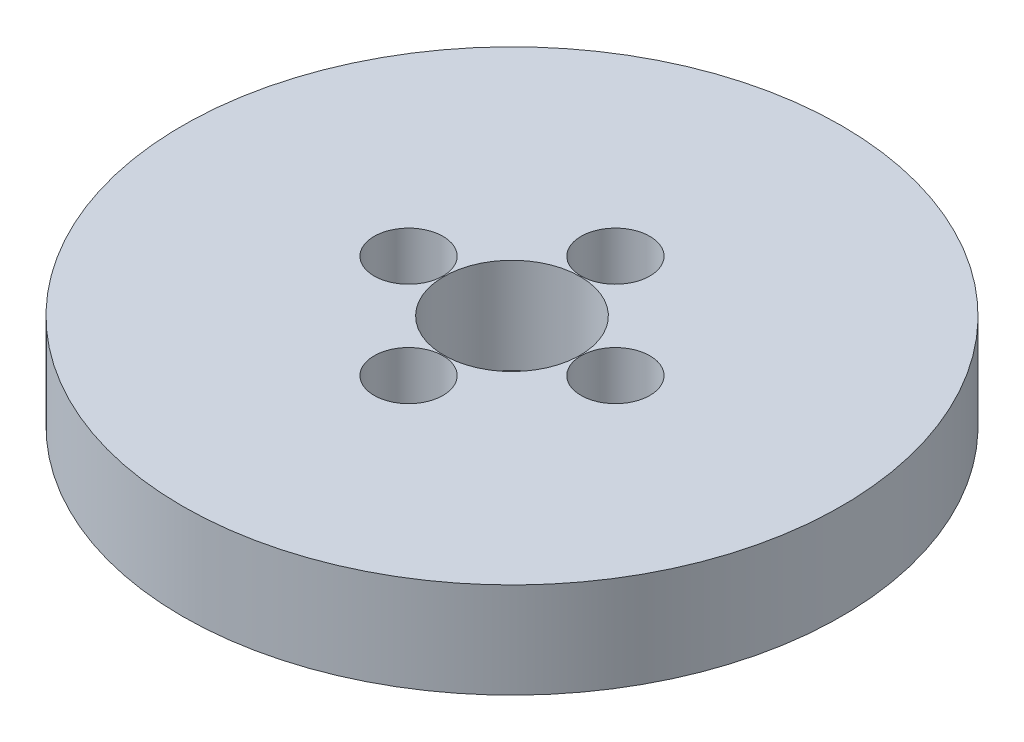
SolidWorks part; units mm, degrees
ref_plane "Front Plane" through (0, 0, 0) normal (0, 0, 1) x (1, 0, 0)
ref_plane "Top Plane" through (0, 0, 0) normal (0, 1, 0) x (1, 0, 0)
ref_plane "Right Plane" through (0, 0, 0) normal (1, 0, 0) x (0, 0, -1)
sketch "Sketch1" plane through (0, 0, 0) normal (0, 1, 0) x (1, 0, 0)
  circle A0 centre (0, 0) radius 72.5
  dimension "FLANGE_OD" = 145
extrude "Boss-Extrude1" add sketch "Sketch1" along normal blind 21
sketch "Sketch2" plane through (0, 0, 0) normal (0, 1, 0) x (1, 0, 0)
  circle A0 centre (0, 0) radius 15
  dimension "BORE_D" = 30
extrude "Cut-Extrude1" cut sketch "Sketch2" along normal through all
sketch "Sketch3" plane through (0, 21, 0) normal (0, 1, 0) x (1, 0, 0)
  circle A0 centre (0, 0) radius 22.7547 construction
  circle A1 centre (-22.7547, 0) radius 7.5702
  dimension "BOLT_D" = 15.1404
  dimension "BOLT_PCD" = 45.5093
extrude "Cut-Extrude2" cut sketch "Sketch3" against normal blind 15.4364
pattern_circular "CirPattern1" count 4 over 360 about axis through (0, 0, 0) along (0, 1, 0) of "Cut-Extrude2"
